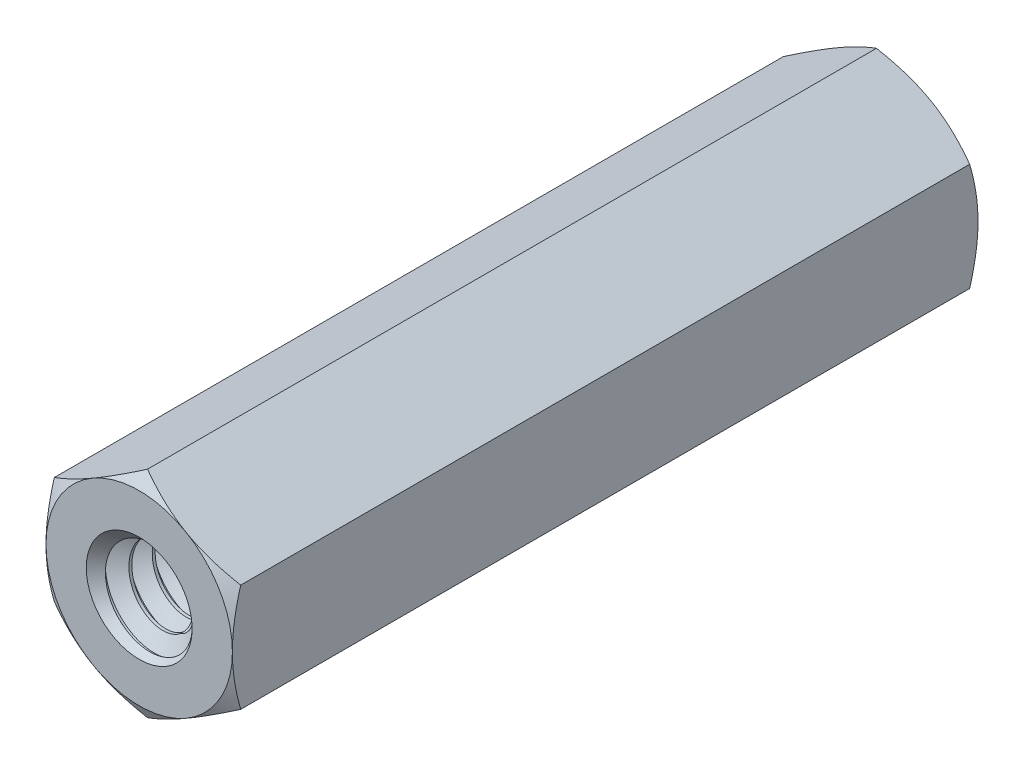
SolidWorks part; units mm, degrees
ref_plane "Front Plane" through (0, 0, 0) normal (0, 0, 1) x (1, 0, 0)
ref_plane "Top Plane" through (0, 0, 0) normal (0, 1, 0) x (1, 0, 0)
ref_plane "Right Plane" through (0, 0, 0) normal (1, 0, 0) x (0, 0, -1)
sketch "Sketch3" plane through (0, 0, 0) normal (1, 0, 0) x (0, 0, -1)
  line L0 (-12.7, 0) -> (12.7, 0) construction
  line L1 (0, 3.175) -> (0, -3.175) construction
  line L2 (-12.7, 1.7526) -> (-12.7, -1.7526) construction
  point P2 (-3.175, 0)
  point P3 (3.175, 0)
  dimension "D1" = 15.875
  dimension "Length" = 25.4
  dimension "Min Thread Length" = 15.875
  dimension "Thread Dia" = 3.5052
  dimension "Hex" = 6.35
sketch "Sketch1" plane through (0, 0, 0) normal (0, 0, 1) x (1, 0, 0)
  line L1 (0, 3.6662) -> (-3.175, 1.8331)
  line L2 (-3.175, 1.8331) -> (-3.175, -1.8331)
  line L3 (-3.175, -1.8331) -> (0, -3.6662)
  line L4 (0, -3.6662) -> (3.175, -1.8331)
  line L5 (3.175, -1.8331) -> (3.175, 1.8331)
  line L6 (3.175, 1.8331) -> (0, 3.6662)
  circle A0 centre (0, 0) radius 3.175 construction
  circle A1 centre (0, 0) radius 1.7526
extrude "Extrude1" add sketch "Sketch1" along normal up to vertex (12.7 mm away) and the other way up to vertex (12.7 mm away) up to point (0, 0, 12.7) other way up to point (0, 0, -12.7)
sketch "Sketch11" plane through (0, 0, -12.7) normal (0, 0, -1) x (-1, 0, 0)
  circle A0 centre (0, 0) radius 1.7526 construction
  circle A1 centre (0, 0) radius 1.7526
curve "Helix/Spiral1" pitch 0.7937 height 26.1937 turns 33 parameters "Pitch"=0.7937
sketch "Sketch12" plane through (0, 0, 0) normal (1, 0, 0) x (0, 0, -1)
  line L0 (13.3945, 1.7526) -> (12.7, 1.7526)
  line L1 (13.3945, 1.7526) -> (13.0969, 1.237)
  line L2 (13.0969, 1.237) -> (12.9977, 1.237)
  line L3 (12.9977, 1.237) -> (12.7, 1.7526)
  line L4 (13.0473, 1.237) -> (13.0473, 1.7526) construction
  line L5 (13.2457, 1.4948) -> (12.8488, 1.4948) construction
  dimension "D1" = 0.0992
  dimension "D2" = 0.3969
  dimension "D3" = 60
sweep "Sweep1" add profiles "Sketch12" path "Helix/Spiral1"
sketch "Sketch6" plane through (0, 0, -12.7) normal (0, 0, -1) x (-1, 0, 0)
  line L6 (0, 3.6662) -> (-3.175, 1.8331)
  line L7 (-3.175, 1.8331) -> (-3.175, -1.8331)
  line L8 (-3.175, -1.8331) -> (0, -3.6662)
  line L9 (0, -3.6662) -> (3.175, -1.8331)
  line L10 (3.175, -1.8331) -> (3.175, 1.8331)
  line L11 (3.175, 1.8331) -> (0, 3.6662)
  line L12 (0, 3.6662) -> (-3.175, 1.8331)
  line L13 (-3.175, 1.8331) -> (-3.175, -1.8331)
  line L14 (-3.175, -1.8331) -> (0, -3.6662)
  line L15 (0, -3.6662) -> (3.175, -1.8331)
  line L16 (3.175, -1.8331) -> (3.175, 1.8331)
  line L17 (3.175, 1.8331) -> (0, 3.6662)
  dimension "D1" = 0
extrude "Extrude2" cut sketch "Sketch6" along normal through all
sketch "Sketch7" plane through (0, 0, -12.7) normal (0, 0, -1) x (-1, 0, 0)
  circle A2 centre (0, 0) radius 1.8034
  circle A3 centre (0, 0) radius 1.8034
  dimension "D1" = 0.0508
extrude "Extrude3" cut sketch "Sketch7" against normal through all draft 43
sketch "Sketch8" plane through (0, 0, -12.7) normal (0, 0, -1) x (-1, 0, 0)
  circle A0 centre (0, 0) radius 3.175 construction
  circle A1 centre (0, 0) radius 3.175
extrude "Extrude4" cut sketch "Sketch8" against normal through all draft 60 flip side to cut
mirror "Mirror1" about plane through (0, 0, 0) normal (0, 0, 1) of "Extrude2", "Extrude3", "Extrude4"
sketch "Sketch9" [suppressed] plane through (0, 0, 0) normal (1, 0, 0) x (0, 0, -1)
  line L1 (-22.225, 3.2258) -> (22.225, 3.2258)
  line L2 (-22.225, 3.2258) -> (-22.225, 0)
  line L3 (-22.225, 0) -> (22.225, 0)
  line L4 (22.225, 3.2258) -> (22.225, 0)
  line L7 (-38.1, 0) -> (38.1, 0) construction
revolve "Revolve" [suppressed] add sketch "Sketch9" angle 360 about L0
sketch "Sketch10" [suppressed] plane through (0, 0, 0) normal (1, 0, 0) x (0, 0, -1)
  line L0 (38.1, 3.175) -> (22.225, 3.175)
  line L1 (-38.1, 3.175) -> (-22.225, 3.175)
  line L2 (22.225, 3.175) -> (22.225, -3.175)
  line L3 (-38.1, -3.2258) -> (-22.225, -3.2258)
  line L4 (-22.225, 3.175) -> (-22.225, -3.2258)
  line L5 (22.225, -3.175) -> (38.1, -3.175)
equation "\"D1@Sketch3\" = \"Min Thread Length@Sketch3\""
equation "\"D3@Helix/Spiral1\" = \"Length@Sketch3\"+\"Pitch@Helix/Spiral1\""
equation "\"D1@Sketch12\" = \"Pitch@Helix/Spiral1\"*.125"
equation "\"D2@Sketch12\" = \"Pitch@Helix/Spiral1\"*.5"
